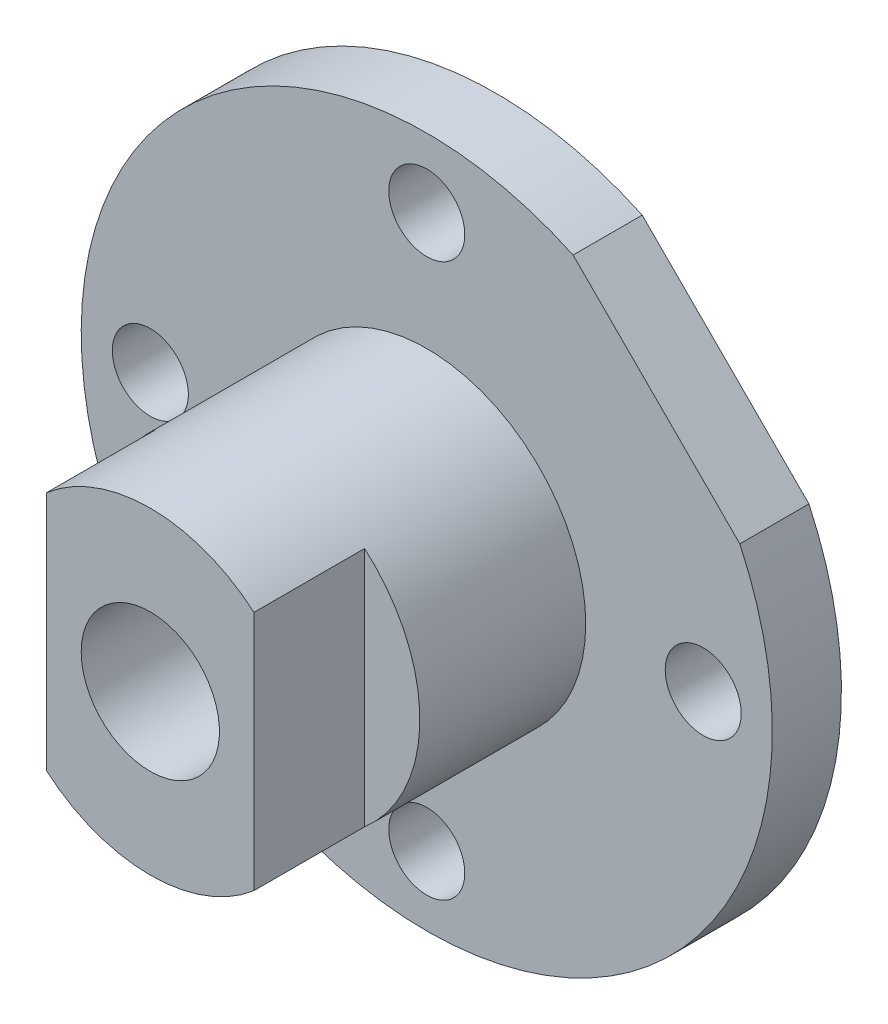
SolidWorks part; units mm, degrees
ref_plane "Front Plane" through (0, 0, 0) normal (0, 0, 1) x (1, 0, 0)
ref_plane "Top Plane" through (0, 0, 0) normal (0, 1, 0) x (1, 0, 0)
ref_plane "Right Plane" through (0, 0, 0) normal (1, 0, 0) x (0, 0, -1)
sketch "Sketch1" plane through (0, 0, 0) normal (0, 0, 1) x (1, 0, 0)
  circle A0 centre (0, 0) radius 11.5
  dimension "D1" = 23
extrude "Boss-Extrude1" add sketch "Sketch1" along normal blind 25
sketch "Sketch2" plane through (0, 0, 0) normal (0, 0, -1) x (-1, 0, 0)
  circle A0 centre (0, 0) radius 25
  dimension "D1" = 50
extrude "Boss-Extrude2" add sketch "Sketch2" against normal blind 5
sketch "Sketch3" plane through (0, 0, 0) normal (0, 0, -1) x (-1, 0, 0)
  circle A0 centre (0, 0) radius 5
  dimension "D1" = 10
extrude "Cut-Extrude1" cut sketch "Sketch3" against normal through all
sketch "Sketch4" plane through (0, 0, 0) normal (0, 0, -1) x (-1, 0, 0)
  line L1 (8, 0) -> (4, 6.9282)
  line L2 (4, 6.9282) -> (-4, 6.9282)
  line L3 (-4, 6.9282) -> (-8, 0)
  line L4 (-8, 0) -> (-4, -6.9282)
  line L5 (-4, -6.9282) -> (4, -6.9282)
  line L6 (4, -6.9282) -> (8, 0)
  circle A0 centre (0, 0) radius 6.9282 construction
  dimension "D1" = 16
extrude "Cut-Extrude2" cut sketch "Sketch4" against normal blind 10
sketch "Sketch5" plane through (0, 0, 0) normal (0, 1, 0) x (1, 0, 0)
  line L1 (11.5, -25) -> (7.5, -25)
  line L2 (11.5, -25) -> (11.5, -17)
  line L3 (11.5, -17) -> (7.5, -17)
  line L4 (7.5, -25) -> (7.5, -17)
  dimension "D1" = 7.5
  dimension "D2" = 8
extrude "Cut-Extrude3" cut sketch "Sketch5" against normal through all and the other way through all
mirror "Mirror1" about plane through (0, 0, 0) normal (1, 0, 0) of "Cut-Extrude3"
hole_wizard "M5 Clearance Hole1" positions "Sketch7" profile "Sketch6" hole size "M5" standard "ANSI Metric" end condition through all
sketch "Sketch7" plane through (0, 0, 0) normal (0, 0, -1) x (-1, 0, 0)
  circle A0 centre (0, 0) radius 20 construction
  point P0 (0, 20)
  point P13 (-20, 0)
  point P15 (20, 0)
  point P17 (0, -20)
  dimension "D1" = 40
sketch "Sketch6" plane through (0, 20, 0) normal (1, 0, 0) x (0, 1, 0)
  line L0 (0, 0) -> (0, 25)
  line L1 (0, 25) -> (2.75, 25)
  line L2 (2.75, 25) -> (2.75, 0)
  line L5 (2.75, 0) -> (0, 0)
  line L11 (0, -6.35) -> (0, 107.95) construction
  dimension "Thru Hole Dia." = 5.5
  dimension "Thru Hole Depth" = 25
sketch "Sketch8" plane through (0, 0, 0) normal (0, 0, -1) x (-1, 0, 0)
  line L0 (-22.6482, 10.5858) -> (-10.5858, 22.6482)
  line L1 (0, 0) -> (-16.617, 16.617) construction
  line L2 (0, 0) -> (0, 25) construction
  circle A0 centre (0, 0) radius 25 construction
  arc A1 (-10.5858, 22.6482) -> (-22.6482, 10.5858) centre (0, 0) ccw
  dimension "D1" = 45
  dimension "D2" = 23.5
extrude "Cut-Extrude4" cut sketch "Sketch8" against normal through all
